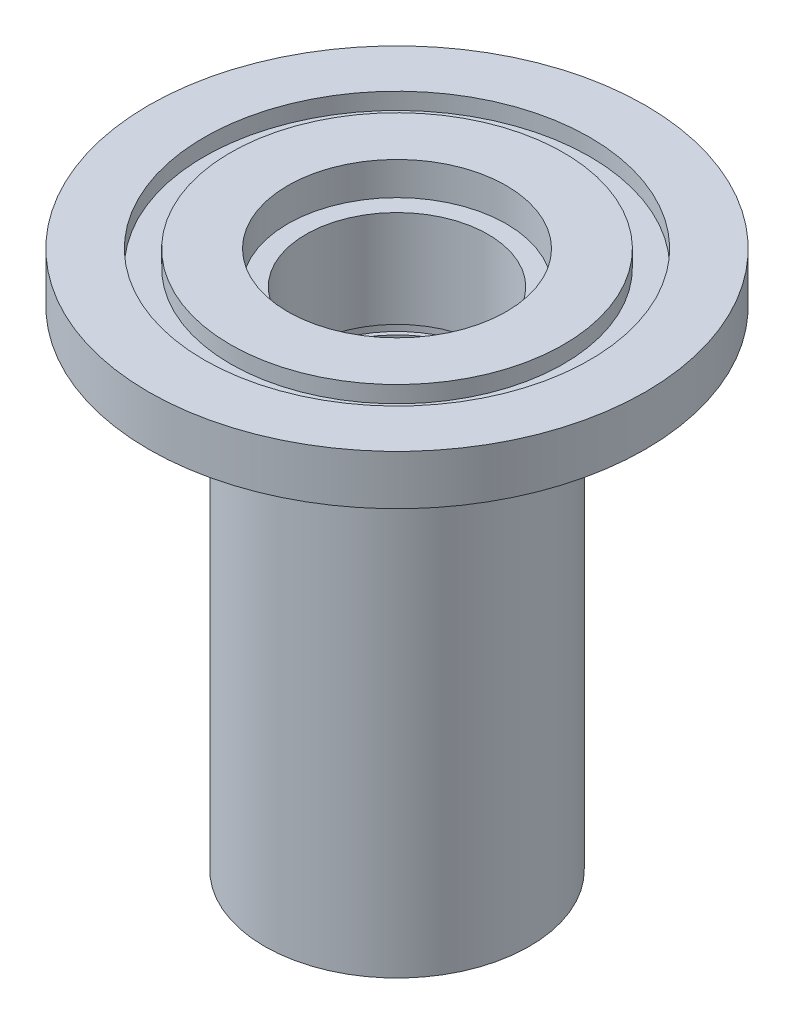
SolidWorks part; units mm, degrees
ref_plane "Front Plane" through (0, 0, 0) normal (0, 0, 1) x (1, 0, 0)
ref_plane "Top Plane" through (0, 0, 0) normal (0, 1, 0) x (1, 0, 0)
ref_plane "Right Plane" through (0, 0, 0) normal (1, 0, 0) x (0, 0, -1)
sketch "Sketch1" plane through (0, 0, 0) normal (0, 0, 1) x (1, 0, 0)
  line L0 (0, 0) -> (0, -122.9972) construction
  line L1 (30, 0) -> (23.2936, 0)
  line L2 (13.2, 0) -> (13.2, -4)
  line L3 (13.2, -4) -> (11, -4)
  line L4 (11, -4) -> (11, -15.7)
  line L9 (11, -65) -> (16, -65)
  line L10 (16, -65) -> (16, -6)
  line L11 (16, -6) -> (30, -6)
  line L12 (30, -6) -> (30, 0)
  line L13 (11, -16.8) -> (11, -31.2)
  line L14 (11, -15.7) -> (11.5, -15.7)
  line L16 (11, -16.8) -> (11.5, -16.8)
  line L17 (11.5, -15.7) -> (11.5, -16.8)
  line L18 (11, -31.2) -> (11.5, -31.2)
  line L20 (11, -32.3) -> (11.5, -32.3)
  line L21 (11.5, -31.2) -> (11.5, -32.3)
  line L22 (11, -32.3) -> (11, -65)
  line L23 (20.1082, 0) -> (20.1082, -2.0157)
  line L24 (20.1082, -2.0157) -> (23.2936, -2.0157)
  line L25 (23.2936, -2.0157) -> (23.2936, 0)
  line L26 (20.1082, 0) -> (13.2, 0)
  point P21 (23.2936, -2.0157)
  dimension "D1" = 22
  dimension "D2" = 26.4
  dimension "D3" = 4
  dimension "D4" = 15.7
  dimension "D5" = 1.1
  dimension "D6" = 23
  dimension "D7" = 32.3
  dimension "D8" = 65
  dimension "D9" = 6
  dimension "D10" = 32
  dimension "D11" = 60
revolve "Revolve1" add sketch "Sketch1" angle 360 about L0
